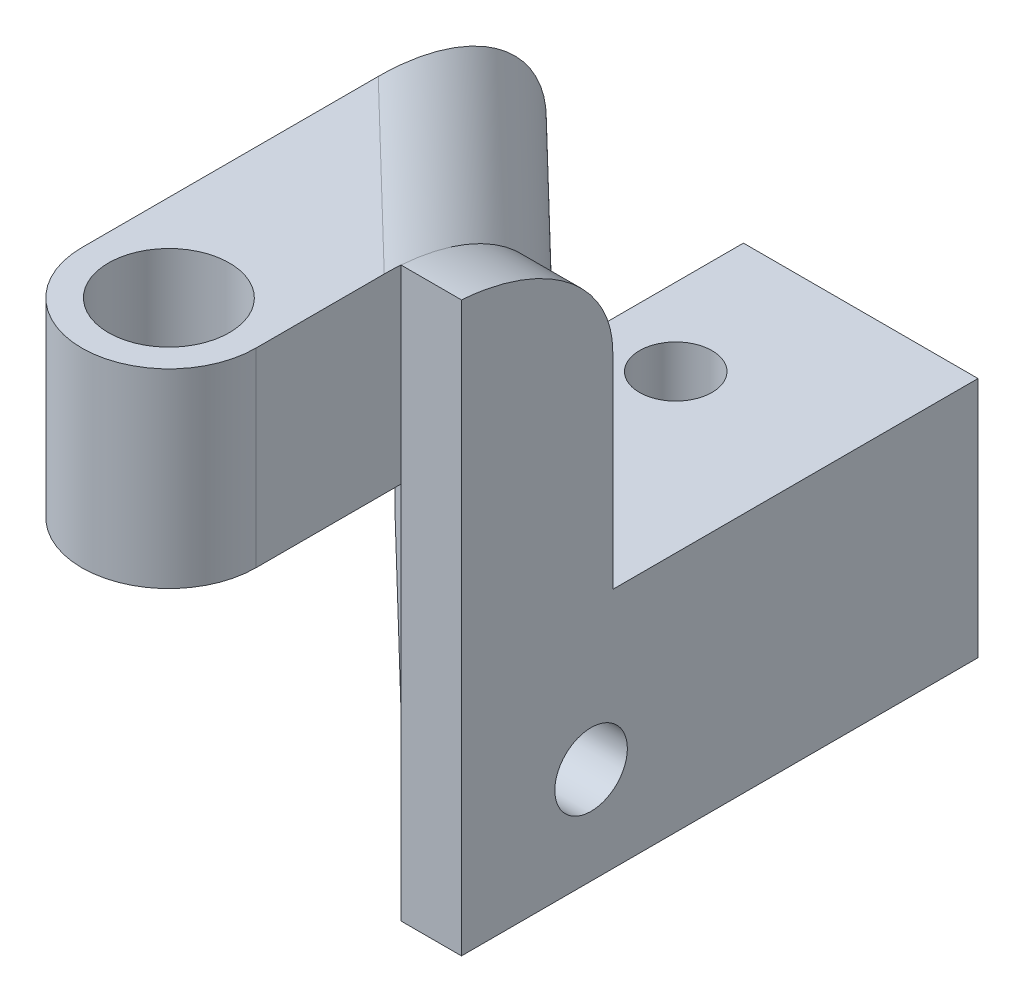
SolidWorks part; units mm, degrees
note: The reader was unsure of these and kept them because the rebuilt part matched: shared geometry of "Croquis1<3>", "Croquis1<6>".
ref_plane "Front Plane" through (0, 0, 0) normal (0, 0, 1) x (1, 0, 0)
ref_plane "Top Plane" through (0, 0, 0) normal (0, 1, 0) x (1, 0, 0)
ref_plane "Right Plane" through (0, 0, 0) normal (1, 0, 0) x (0, 0, -1)
sketch "Croquis1" plane through (0, 0, 0) normal (0, 1, 0) x (1, 0, 0)
  line L5 (-3.6, 27.36) -> (-3.6, 0)
  line L6 (3.6, 0) -> (3.6, 27.36)
  line L7 (3.6, 27.36) -> (-3.6, 27.36)
  line L8 (-3.6, 12.953) -> (3.6, 6)
  line L9 (0, 0) -> (-2.5, 0) construction
  line L10 (-3.6, 19.2087) -> (3.6, 12.2557)
  arc A5 (-3.6, 0) -> (3.6, 0) centre (0, 0) ccw
  circle A6 centre (0, 0) radius 2.5
  circle A7 centre (-0.4, 21.36) radius 1.5
  dimension "D1" = 3.6
  dimension "D10" = 3
  dimension "D6" = 5
  dimension "D3" = 27.36
  dimension "D7" = 44
  dimension "D8" = 6
  dimension "D9" = 4.5
  dimension "D11" = 6
  dimension "D12" = 4
extrude "Saliente-Extruir1" add sketch "Croquis1" along normal blind 2.5
extrude "Saliente-Extruir2" add sketch "Croquis1<3>" along normal blind 7.87 from offset 8.15 separate body
sketch "Croquis1<3>" plane through (0, 0, 0) normal (0, 1, 0) x (1, 0, 0) same geometry as "Croquis1"
extrude "Saliente-Extruir5" add sketch "Croquis1<6>" along normal up to surface (16.02 mm away) contours L10 L5 L8 L6 up to face at (0, 16.02, 2.5)
sketch "Croquis1<6>" plane through (0, 0, 0) normal (0, 1, 0) x (1, 0, 0) same geometry as "Croquis1"
fillet "Redondeo3" radius 5 1 edges at (0, 16.02, -15.7322)
sketch "Croquis8" plane through (3.6, 0, 0) normal (1, 0, 0) x (0, 0, -1)
  line L0 (6, 8.15) -> (6, 15.9949)
  line L1 (6, -7.5) -> (27.36, -7.5)
  line L8 (12.2557, 2.5) -> (12.2557, 11.02)
  line L9 (5.3049, 16.02) -> (0, 16.02)
  line L10 (0, 16.02) -> (0, 8.15)
  line L11 (0, 8.15) -> (6, 8.15)
  line L12 (6, 8.15) -> (6, 0)
  line L13 (6, 0) -> (27.36, 0)
  line L14 (27.36, 0) -> (27.36, 2.5)
  line L15 (27.36, 2.5) -> (12.2557, 2.5)
  line L16 (12.2557, 2.5) -> (12.2557, 11.02)
  line L17 (5.3049, 16.02) -> (0, 16.02)
  line L18 (0, 16.02) -> (0, 8.15)
  line L19 (0, 8.15) -> (6, 8.15)
  line L20 (6, 8.15) -> (6, -7.5)
  line L22 (27.36, -7.5) -> (27.36, 2.5)
  line L23 (27.36, 2.5) -> (12.2557, 2.5)
  circle A0 centre (11.36, -3.5) radius 1.5
  ellipse E1 centre (5.3049, 11.02) end of major axis (12.2557, 11.02) minor radius 5 (12.2557, 11.02) -> (5.3049, 16.02) ccw
  ellipse E2 centre (5.3049, 11.02) end of major axis (12.2557, 11.02) minor radius 5 (12.2557, 11.02) -> (5.3049, 16.02) ccw
  line M10 (12.2557, 2.5) -> (12.2557, 11.02)
  ellipse M11 centre (5.3049, 11.02) end of major axis (-1.6459, 11.02) minor radius 5 (12.2557, 11.02) -> (5.3049, 16.02) ccw
  line M15 (6, 8.15) -> (6, 0)
  line M16 (6, 0) -> (27.36, 0)
  line M17 (27.36, 0) -> (27.36, 2.5)
  line M18 (27.36, 2.5) -> (12.2557, 2.5)
  dimension "D3" = 3
  dimension "D2" = 10
  dimension "D4" = 4
  dimension "D5" = 16
  dimension "D1" = 0
extrude "Saliente-Extruir6" add sketch "Croquis8" along normal blind 2.5 contours L1 L22 L20 M16 | L0 M15 M16 M17 M18 M10 M11
